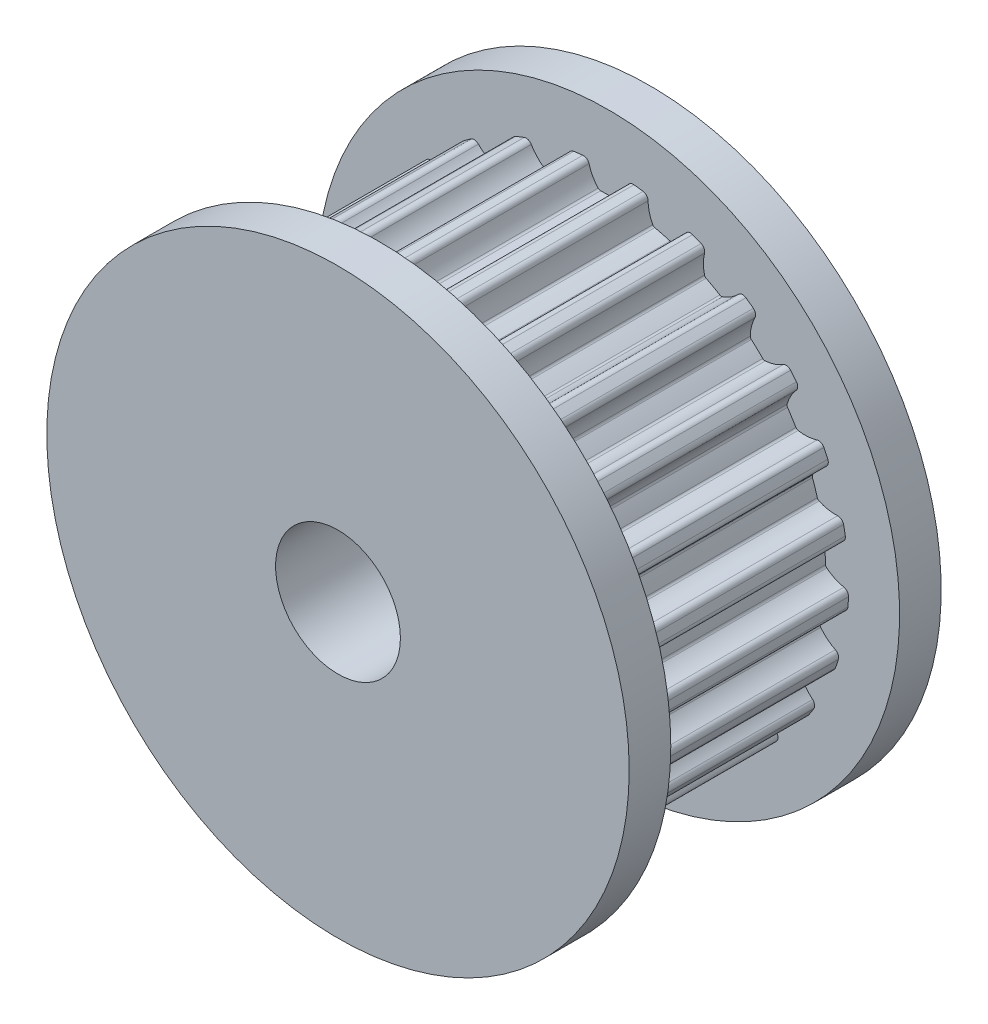
SolidWorks part; units mm, degrees
material "6061-T6 (SS)"
ref_plane "前基準面" through (0, 0, 0) normal (0, 0, 1) x (1, 0, 0)
ref_plane "上基準面" through (0, 0, 0) normal (0, 1, 0) x (1, 0, 0)
ref_plane "右基準面" through (0, 0, 0) normal (1, 0, 0) x (0, 0, -1)
sketch "草圖1" plane through (0, 0, 0) normal (0, 0, 1) x (1, 0, 0)
  circle A0 centre (0, 0) radius 11.555
  dimension "D1" = 23.11
extrude "填料-伸長1" add sketch "草圖1" along normal mid plane 11
sketch "草圖2" plane through (0, 0, 5.5) normal (0, 0, 1) x (1, 0, 0)
  line L0 (0, 0) -> (0, 11.555) construction
  line L1 (0, 11.555) -> (0, 11.809) construction
  line L2 (-0.975, 11.809) -> (0.975, 11.809) construction
  circle A0 centre (0, 0) radius 11.555 construction
  arc A1 (-0.3761, 10.4382) -> (0.3761, 10.4382) centre (0, 0) cw
  arc A2 (-0.3761, 10.4382) -> (-0.493, 10.4878) centre (-0.3815, 10.5881) cw
  arc A3 (-0.493, 10.4878) -> (-0.9293, 11.2853) centre (0.975, 11.809) cw
  arc A4 (-1.2291, 11.4894) -> (-0.9293, 11.2853) centre (-1.1993, 11.211) cw
  arc A5 (0.3761, 10.4382) -> (0.493, 10.4878) centre (0.3815, 10.5881) ccw
  arc A6 (0.493, 10.4878) -> (0.9293, 11.2853) centre (-0.975, 11.809) ccw
  arc A7 (1.2291, 11.4894) -> (0.9293, 11.2853) centre (1.1993, 11.211) ccw
  arc A8 (-1.2291, 11.4894) -> (1.2291, 11.4894) centre (0, 0) cw
  dimension "D1" = 0.15
  dimension "D2" = 1.975
  dimension "D3" = 0.28
  dimension "D4" = 1.11
  dimension "D5" = 0.254
  dimension "D6" = 1.95
extrude "除料-伸長1" cut sketch "草圖2" against normal through all and the other way through all
pattern_circular "環狀複製排列1" count 25 over 360 about axis through (0, 0, 5.5) along (0, 0, -1) of "除料-伸長1" reverse direction yes
sketch "草圖3" plane through (0, 0, 5.5) normal (0, 0, 1) x (1, 0, 0)
  circle A0 centre (0, 0) radius 14
  dimension "D1" = 28
extrude "填料-伸長2" add sketch "草圖3" along normal blind 2
sketch "草圖9" plane through (0, 0, -5.5) normal (0, 0, -1) x (-1, 0, 0)
  circle A0 centre (0, 0) radius 14
  circle A1 centre (0, 0) radius 14 construction
extrude "填料-伸長3" add sketch "草圖9" along normal blind 2
sketch "草圖4" plane through (0, 0, 7.5) normal (0, 0, 1) x (1, 0, 0)
  circle A0 centre (0, 0) radius 3
  dimension "D1" = 6
extrude "除料-伸長2" cut sketch "草圖4" against normal through all and the other way blind 8
sketch "草圖10" plane through (0, 0, 0) normal (0, 1, 0) x (1, 0, 0)
  circle A0 centre (0, 0) radius 2
  dimension "D1" = 4
extrude "除料-伸長3" cut sketch "草圖10" against normal through all
sketch "草圖11" plane through (0, 0, 0) normal (1, 0, 0) x (0, 0, -1)
  circle A0 centre (0, 0) radius 2
  dimension "D1" = 4
extrude "除料-伸長4" cut sketch "草圖11" against normal through all
